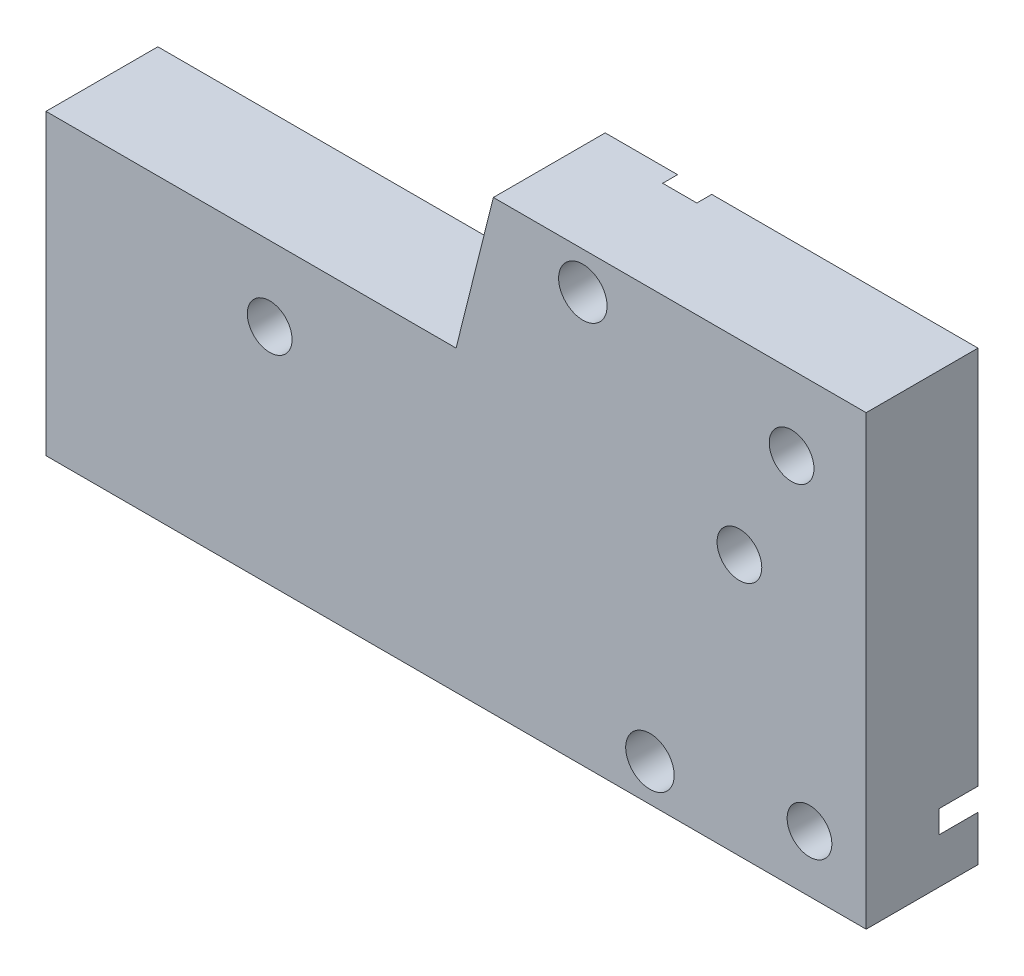
SolidWorks part; units mm, degrees
ref_plane "Front Plane" through (0, 0, 0) normal (0, 0, 1) x (1, 0, 0)
ref_plane "Top Plane" through (0, 0, 0) normal (0, 1, 0) x (1, 0, 0)
ref_plane "Right Plane" through (0, 0, 0) normal (1, 0, 0) x (0, 0, -1)
sketch "Sketch1" plane through (0, 0, 0) normal (0, 0, 1) x (1, 0, 0)
  line L9 (0, 0) -> (110, 0)
  line L10 (110, 0) -> (110, 60)
  line L11 (110, 60) -> (60, 60)
  line L12 (60, 60) -> (55, 40)
  line L13 (55, 40) -> (0, 40)
  line L14 (0, -50) -> (0, 50) construction
  line L15 (0, 40) -> (0, 0)
  circle A0 centre (72, 55) radius 3.25
  circle A1 centre (81, 5) radius 3.25
  circle A2 centre (93, 35) radius 3
  circle A3 centre (30, 30) radius 3
  circle A4 centre (100, 50) radius 3
  circle A5 centre (102.4, 7.6) radius 3
  dimension "D6" = 6.5
  dimension "D7" = 6.5
  dimension "D12" = 6
  dimension "D15" = 6
  dimension "D19" = 6
  dimension "D20" = 6
  dimension "D1" = 110
  dimension "D2" = 60
  dimension "D3" = 40
  dimension "D4" = 55
  dimension "D5" = 50
  dimension "D8" = 5
  dimension "D9" = 12
  dimension "D10" = 5
  dimension "D11" = 21
  dimension "D13" = 35
  dimension "D14" = 17
  dimension "D16" = 30
  dimension "D17" = 30
  dimension "D23" = 7.6
  dimension "D24" = 7.6
  dimension "D25" = 10
  dimension "D26" = 10
extrude "Boss-Extrude1" add sketch "Sketch1" against normal blind 15 contours L13 L15 L9 L10 L11 L12
extrude "Cut-Extrude1" cut sketch "Sketch1<4>" against normal blind 15 contours A2 | A3
sketch "Sketch1<4>" plane through (0, 0, 0) normal (0, 0, 1) x (1, 0, 0) same geometry as "Sketch1"
extrude "Cut-Extrude2" cut sketch "Sketch1<5>" against normal blind 15 contours A4 | A5
sketch "Sketch1<5>" plane through (0, 0, 0) normal (0, 0, 1) x (1, 0, 0) same geometry as "Sketch1"
sketch "Sketch2" plane through (0, 0, -15) normal (0, 0, -1) x (-1, 0, 0)
  circle A0 centre (-100, 50) radius 7.75
  circle A1 centre (-93, 35) radius 7.75
  circle A2 centre (-102.4, 7.6) radius 7.75
  circle A3 centre (-30, 30) radius 7.75
  dimension "D1" = 15.5
  dimension "D2" = 15.5
  dimension "D3" = 15.5
  dimension "D5" = 15.5
extrude "Cut-Extrude3" cut sketch "Sketch2" against normal blind 5.2 contours A2 | A3 | A1 | A0
extrude "Cut-Extrude4" cut sketch "Sketch1<6>" against normal through all both contours A1 | A0
sketch "Sketch1<6>" plane through (0, 0, 0) normal (0, 0, 1) x (1, 0, 0) same geometry as "Sketch1"
sketch "Sketch3" plane through (0, 0, -15) normal (0, 0, -1) x (-1, 0, 0)
  circle A0 centre (-72, 55) radius 5.5
  circle A1 centre (-81, 5) radius 5.5
  dimension "D1" = 11
  dimension "D2" = 11
extrude "Cut-Extrude13" cut sketch "Sketch3" against normal blind 2
